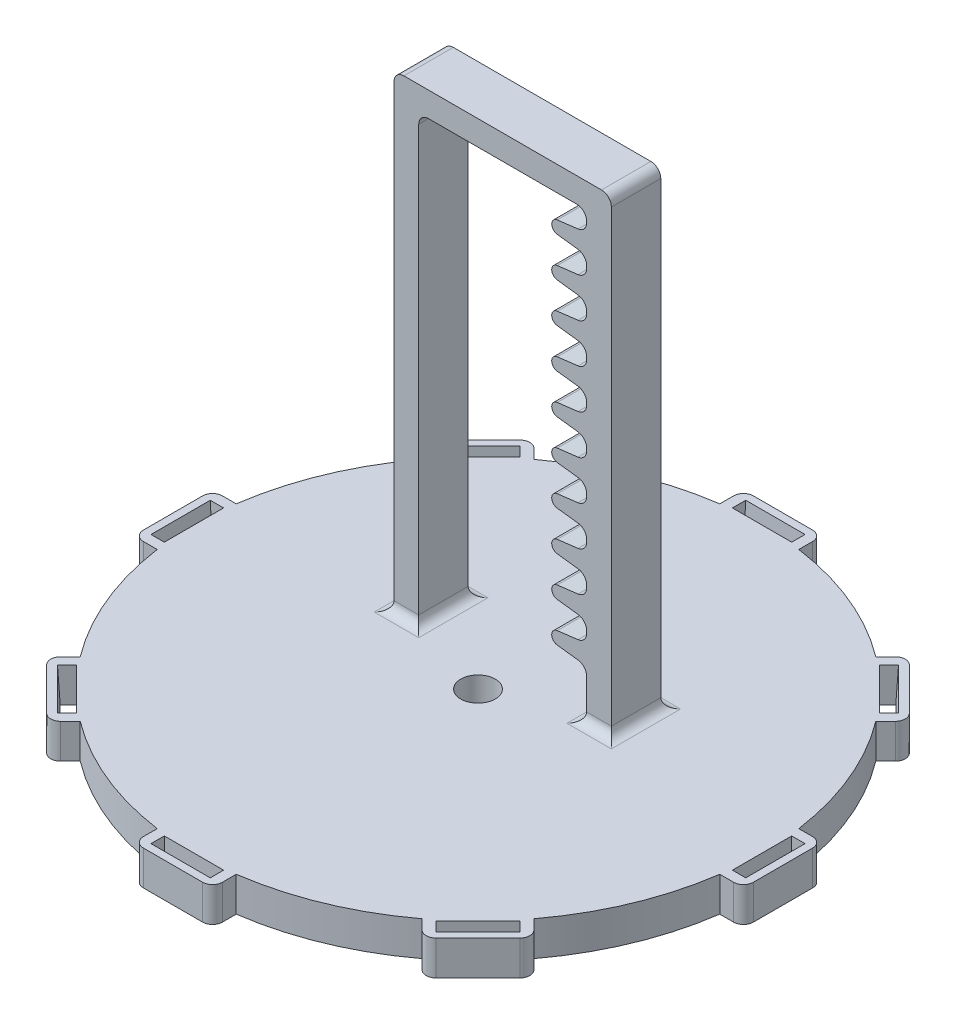
SolidWorks part; units mm, degrees
ref_plane "Front Plane" through (0, 0, 0) normal (0, 0, 1) x (1, 0, 0)
ref_plane "Top Plane" through (0, 0, 0) normal (0, 1, 0) x (1, 0, 0)
ref_plane "Right Plane" through (0, 0, 0) normal (1, 0, 0) x (0, 0, -1)
sketch "Sketch1" plane through (0, 0, 0) normal (0, 1, 0) x (1, 0, 0)
  line L0 (-8, 56.9408) -> (-8, 59.7408)
  line L1 (0, 57.5) -> (0, -57.5) construction
  line L2 (8, 56.9408) -> (8, 59.7408)
  line L3 (-6, 61.7408) -> (6, 61.7408)
  line L4 (39.4147, 47.8999) -> (47.8999, 39.4147)
  line L9 (34.6063, 45.9201) -> (36.5862, 47.8999)
  line L10 (45.9201, 34.6063) -> (47.8999, 36.5862)
  line L15 (61.7408, 6) -> (61.7408, -6)
  line L16 (56.9408, 8) -> (59.7408, 8)
  line L17 (56.9408, -8) -> (59.7408, -8)
  line L22 (47.8999, -39.4147) -> (39.4147, -47.8999)
  line L23 (45.9201, -34.6063) -> (47.8999, -36.5862)
  line L24 (34.6063, -45.9201) -> (36.5862, -47.8999)
  line L29 (6, -61.7408) -> (-6, -61.7408)
  line L30 (8, -56.9408) -> (8, -59.7408)
  line L31 (-8, -56.9408) -> (-8, -59.7408)
  line L36 (-39.4147, -47.8999) -> (-47.8999, -39.4147)
  line L37 (-34.6063, -45.9201) -> (-36.5862, -47.8999)
  line L38 (-45.9201, -34.6063) -> (-47.8999, -36.5862)
  line L43 (-61.7408, -6) -> (-61.7408, 6)
  line L44 (-56.9408, -8) -> (-59.7408, -8)
  line L45 (-56.9408, 8) -> (-59.7408, 8)
  line L50 (-47.8999, 39.4147) -> (-39.4147, 47.8999)
  line L51 (-45.9201, 34.6063) -> (-47.8999, 36.5862)
  line L52 (-34.6063, 45.9201) -> (-36.5862, 47.8999)
  arc A0 (-8, 56.9408) -> (-34.6063, 45.9201) centre (0, 0) ccw
  arc A1 (6, 61.7408) -> (8, 59.7408) centre (6, 59.7408) cw
  arc A2 (-6, 61.7408) -> (-8, 59.7408) centre (-6, 59.7408) ccw
  arc A3 (39.4147, 47.8999) -> (36.5862, 47.8999) centre (38.0005, 46.4857) ccw
  arc A4 (47.8999, 39.4147) -> (47.8999, 36.5862) centre (46.4857, 38.0005) cw
  arc A5 (61.7408, 6) -> (59.7408, 8) centre (59.7408, 6) ccw
  arc A6 (61.7408, -6) -> (59.7408, -8) centre (59.7408, -6) cw
  arc A7 (47.8999, -39.4147) -> (47.8999, -36.5862) centre (46.4857, -38.0005) ccw
  arc A8 (39.4147, -47.8999) -> (36.5862, -47.8999) centre (38.0005, -46.4857) cw
  arc A9 (6, -61.7408) -> (8, -59.7408) centre (6, -59.7408) ccw
  arc A10 (-6, -61.7408) -> (-8, -59.7408) centre (-6, -59.7408) cw
  arc A11 (-39.4147, -47.8999) -> (-36.5862, -47.8999) centre (-38.0005, -46.4857) ccw
  arc A12 (-47.8999, -39.4147) -> (-47.8999, -36.5862) centre (-46.4857, -38.0005) cw
  arc A13 (-61.7408, -6) -> (-59.7408, -8) centre (-59.7408, -6) ccw
  arc A14 (-61.7408, 6) -> (-59.7408, 8) centre (-59.7408, 6) cw
  arc A15 (-47.8999, 39.4147) -> (-47.8999, 36.5862) centre (-46.4857, 38.0005) ccw
  arc A16 (-39.4147, 47.8999) -> (-36.5862, 47.8999) centre (-38.0005, 46.4857) cw
  arc A17 (-45.9201, 34.6063) -> (-56.9408, 8) centre (0, 0) ccw
  arc A18 (-56.9408, -8) -> (-45.9201, -34.6063) centre (0, 0) ccw
  arc A19 (34.6063, 45.9201) -> (8, 56.9408) centre (0, 0) ccw
  arc A20 (-34.6063, -45.9201) -> (-8, -56.9408) centre (0, 0) ccw
  arc A21 (8, -56.9408) -> (34.6063, -45.9201) centre (0, 0) ccw
  arc A22 (45.9201, -34.6063) -> (56.9408, -8) centre (0, 0) ccw
  arc A23 (56.9408, 8) -> (45.9201, 34.6063) centre (0, 0) ccw
  point P11 (8, 61.7408)
  point P14 (-8, 61.7408)
  point P17 (-8, 58.3408)
  point P98 (0, 0)
  dimension "D1" = 115
  dimension "D2" = 2
  dimension "D3" = 16
  dimension "D4" = 2.8
  dimension "D7" = 8
extrude "Boss-Extrude1" add sketch "Sketch1" along normal blind 7
sketch "Sketch2" plane through (0, 7, 0) normal (0, 1, 0) x (1, 0, 0)
  line L0 (-57.5, 0) -> (57.5, 0) construction
  line L1 (0, 0) -> (0, 10) construction
  line L7 (17, 5) -> (22, 5)
  line L14 (0, 10) -> (29.7122, 10) construction
  line L15 (0, 10) -> (-19.5, 10) construction
  line L17 (17, 5) -> (17, 15)
  line L18 (-22, 15) -> (-17, 15)
  line L19 (-22, 15) -> (-22, 5)
  line L20 (-22, 5) -> (-17, 5)
  line L21 (-17, 15) -> (-17, 5)
  line L22 (-22, 15) -> (-17, 5) construction
  line L23 (-22, 5) -> (-17, 15) construction
  line L24 (17, 15) -> (22, 15)
  line L25 (22, 5) -> (22, 15)
  line L26 (17, 5) -> (22, 15) construction
  line L27 (17, 15) -> (22, 5) construction
  circle A0 centre (0, 0) radius 57.5 construction
  point P8 (19.5, 10)
  dimension "D1" = 10
  dimension "D2" = 17
  dimension "D3" = 17
  dimension "D4" = 10
  dimension "D5" = 5
  dimension "D6" = 10
  dimension "D7" = 5
extrude "Boss-Extrude2" add sketch "Sketch2" along normal blind 95
sketch "Sketch15" plane through (0, 0, 0) normal (0, -1, 0) x (1, 0, 0)
  circle A0 centre (0, 0) radius 3.5
  dimension "D1" = 7
extrude "Cut-Extrude3" cut sketch "Sketch15" along direction (0, 1, 0) on the side against the normal up to surface (7 mm away) contours A0 up to face at (0, 7, 0)
sketch "Sketch16" plane through (0, 0, 0) normal (0, -1, 0) x (1, 0, 0)
  line L1 (-6, 59.8) -> (6, 59.8)
  line L2 (-6, 59.8) -> (-6, 57.5)
  line L3 (-6, 57.5) -> (6, 57.5)
  line L4 (6, 59.8) -> (6, 57.5)
  point P5 (0, 57.5)
  dimension "D1" = 2.3
  dimension "D2" = 12
  dimension "D3" = 57.5
sketch "Sketch17" plane through (0, 7, 0) normal (0, 1, 0) x (1, 0, 0)
  line L0 (-6, -57.5) -> (6, -57.5) construction
  line L1 (-6, -57.5) -> (6, -57.5)
  line L2 (-6, -57.5) -> (-6, -60.2)
  line L3 (-6, -60.2) -> (6, -60.2)
  line L4 (6, -60.2) -> (6, -57.5)
  dimension "D1" = 2.7
ref_axis "Axis1" through (0, 107.1, 0) along (0, -1, 0)
loft "Cut-Loft2" cut profiles "Sketch16", "Sketch17" connector at (6, 0, 59.8) connector at (6, 7, 60.2)
pattern_circular "CirPattern1" count 8 over 360 about axis through (0, 107.1, 0) along (0, -1, 0) of "Cut-Loft2"
sketch "Sketch18" plane through (-17, 0, 0) normal (1, 0, 0) x (0, 0, -1)
  line L0 (15, 102) -> (15, 7) construction
  line L1 (5, 102) -> (15, 102)
  line L2 (5, 102) -> (5, 97)
  line L3 (5, 97) -> (15, 97)
  line L4 (15, 102) -> (15, 97)
  dimension "D1" = 5
extrude "Boss-Extrude3" add sketch "Sketch18" along normal up to surface (34 mm away) up to face at (17, 54.5, -10)
sketch "Sketch19" plane through (0, 0, -15) normal (0, 0, -1) x (-1, 0, 0)
  line L0 (-17, 93) -> (-11.0447, 92.2688)
  line L1 (-17, 97) -> (-17, 7) construction
  line L4 (-11, 91) -> (-19.8185, 91) construction
  line L5 (-17, 89) -> (-11.0447, 89.7312)
  line L6 (-17, 93) -> (-17, 89)
  arc A1 (-11.0447, 92.2688) -> (-11.0447, 89.7312) centre (-11.2005, 91) cw
  dimension "D1" = 6
  dimension "D4" = 4
  dimension "D2" = 7
  dimension "D3" = 4
extrude "Boss-Extrude4" add sketch "Sketch19" against normal blind 10
fillet "Fillet1" radius 2 2 edges at (17, 93, -10) (17, 89, -10)
fillet "Fillet2" radius 2 12 edges at (-22, 102, -10) (22, 102, -10) (17, 7, -10) (19.5, 7, -15) (19.5, 7, -5) (22, 7, -10) (-19.5, 7, -5) (-19.5, 7, -15) (-22, 7, -10) (-17, 7, -10) (-17, 97, -10) (17, 97, -10)
pattern_linear "LPattern2" count 10 spacing 8 along (0, -1, 0) of "Fillet1", "Boss-Extrude4"
equation "\"85.00.00mm\"=8500"
